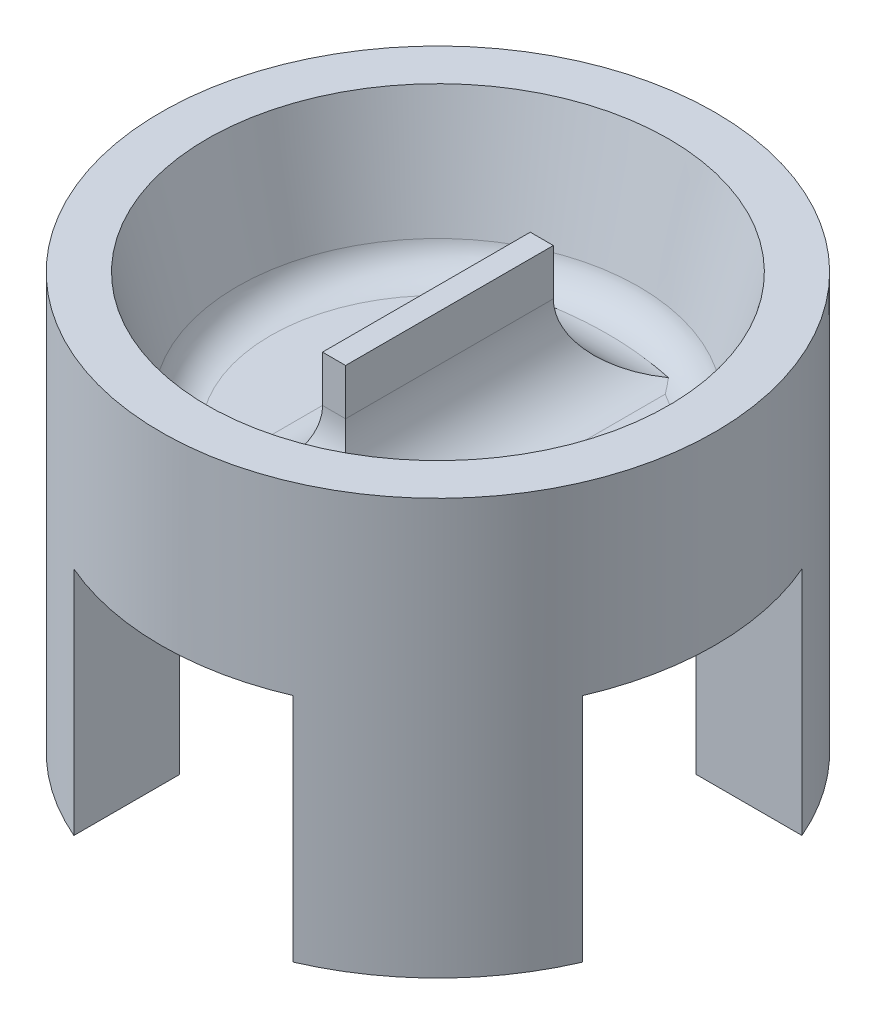
SolidWorks part; units mm, degrees
ref_plane "Front Plane" through (0, 0, 0) normal (0, 0, 1) x (1, 0, 0)
ref_plane "Top Plane" through (0, 0, 0) normal (0, 1, 0) x (1, 0, 0)
ref_plane "Right Plane" through (0, 0, 0) normal (1, 0, 0) x (0, 0, -1)
sketch "Sketch1" plane through (0, 0, 0) normal (0, 1, 0) x (1, 0, 0)
  line L0 (-2.375, 10) -> (2.375, -10) construction
  line L1 (-2.375, 10) -> (2.375, 10)
  line L2 (-2.375, 10) -> (-2.375, 3.2186)
  line L3 (-2.375, -10) -> (2.375, -10)
  line L4 (2.375, 10) -> (2.375, 3.2186)
  line L5 (-10, 2.375) -> (-3.2186, 2.375)
  line L6 (-10, 2.375) -> (-10, -2.375)
  line L7 (-10, -2.375) -> (-3.2186, -2.375)
  line L8 (10, 2.375) -> (10, -2.375)
  line L9 (10, 2.375) -> (-10, -2.375) construction
  line L10 (-2.375, -3.2186) -> (-2.375, -10)
  line L11 (3.2186, 2.375) -> (10, 2.375)
  line L12 (2.375, -3.2186) -> (2.375, -10)
  line L14 (3.2186, -2.375) -> (10, -2.375)
  arc A0 (-3.2186, -2.375) -> (-2.375, -3.2186) centre (0, 0) ccw
  arc A1 (-2.375, 3.2186) -> (-3.2186, 2.375) centre (0, 0) ccw
  arc A2 (3.2186, 2.375) -> (2.375, 3.2186) centre (0, 0) ccw
  arc A3 (2.375, -3.2186) -> (3.2186, -2.375) centre (0, 0) ccw
  dimension "D1" = 8
  dimension "D2" = 4.75
  dimension "D3" = 20
extrude "Boss-Extrude1" add sketch "Sketch1" against normal blind 15
sketch "Sketch2" plane through (0, 0, 0) normal (0, 1, 0) x (1, 0, 0)
  circle A0 centre (0, 0) radius 6
  dimension "D1" = 12
extrude "Boss-Extrude2" add sketch "Sketch2" against normal blind 5 separate body
extrude "Boss-Extrude3" add sketch "Sketch2<2>" along normal blind 1
sketch "Sketch2<2>" plane through (0, 0, 0) normal (0, 1, 0) x (1, 0, 0) same geometry as "Sketch2"
combine bodies "Combine1" operation type subtract main body 103 bodies to subtract 101
sketch "Sketch3" plane through (0, 0, 0) normal (0, 1, 0) x (1, 0, 0)
  line L1 (-0.25, 2.25) -> (0.25, 2.25)
  line L2 (-0.25, 2.25) -> (-0.25, -2.25)
  line L3 (-0.25, -2.25) -> (0.25, -2.25)
  line L4 (0.25, 2.25) -> (0.25, -2.25)
  point P4 (0, -2.25)
  point P6 (0.25, 0)
  dimension "D1" = 4.5
  dimension "D2" = 0.5
extrude "Boss-Extrude4" add sketch "Sketch3" along normal blind 2.5 from surface starting at face at (0, 1, 6)
fillet "Fillet1" radius 1.5 2 edges at (-0.25, 1, 0) (0.25, 1, 0)
fillet "Fillet2" radius 1.5 2 edges at (0, 1, -2.25) (0, 1, 2.25)
sketch "Sketch4" plane through (0, 0, 0) normal (1, 0, 0) x (0, 0, -1)
  line L0 (-6, 1) -> (-6, 4)
  line L1 (6, 1) -> (-6, 1) construction
  line L2 (-6, 4) -> (-5, 4)
  line L3 (-5, 4) -> (-4.2, 1)
  line L4 (-4.2, 1) -> (-6, 1)
  line L5 (-6, 1) -> (-6, 0) construction
  line L6 (0, 0) -> (0, 7.4706) construction
  dimension "D1" = 3
  dimension "D2" = 1
  dimension "D3" = 1.8
revolve "Revolve1" add sketch "Sketch4" angle 360 about L6
fillet "Fillet3" radius 0.75 1 edges at (0, 1, -4.2)
